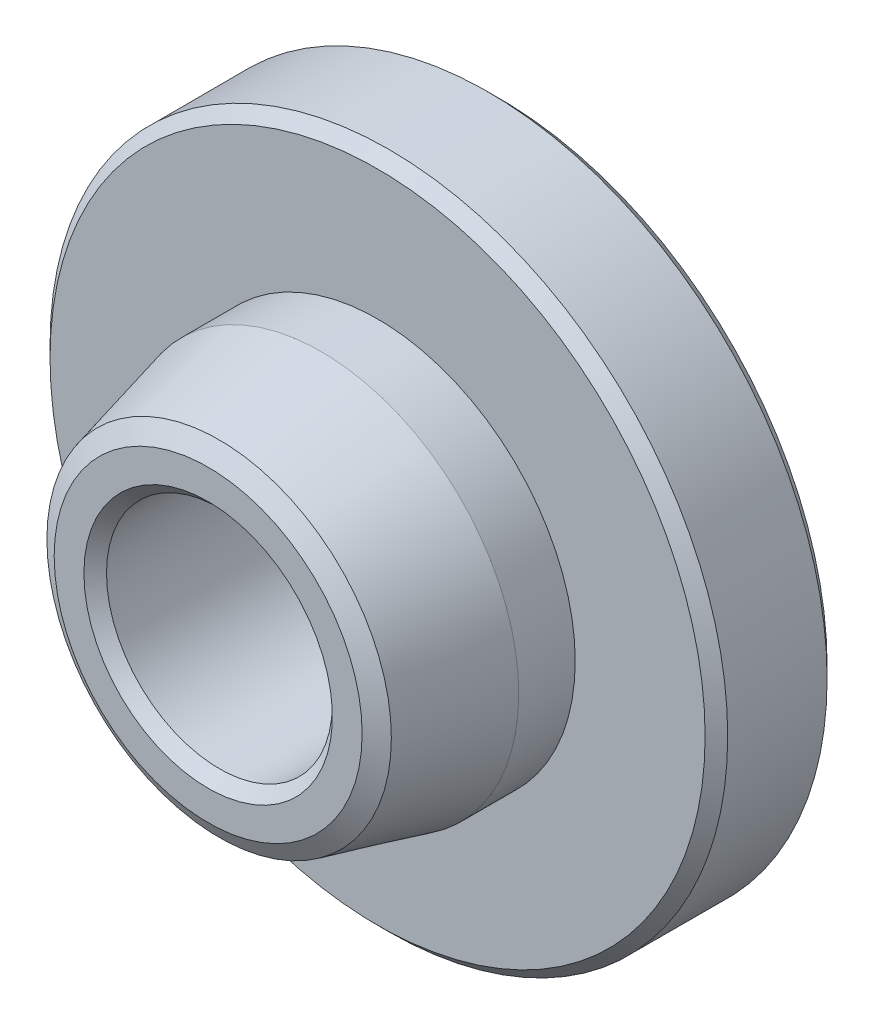
SolidWorks part; units mm, degrees
ref_plane "Ebene vorne" through (0, 0, 0) normal (0, 0, 1) x (1, 0, 0)
ref_plane "Ebene oben" through (0, 0, 0) normal (0, 1, 0) x (1, 0, 0)
ref_plane "Ebene rechts" through (0, 0, 0) normal (1, 0, 0) x (0, 0, -1)
ref_axis "Achse1" through (0, 0, -1.629) along (0, 0, 1)
sketch "Skizze1" plane through (0, 0, 0) normal (1, 0, 0) x (0, 0, -1)
  line L0 (0, 21.2) -> (0, -20.4348) construction
  line L1 (-23.4087, 0) -> (24.2783, 0) construction
  line L2 (0, 2) -> (-4.66, 2)
  line L3 (-4.66, 2) -> (-4.66, 3.0013)
  line L4 (-4.66, 3.0013) -> (-2.66, 3.5)
  line L5 (-2.66, 3.5) -> (-1.66, 3.5)
  line L6 (-1.66, 3.5) -> (-1.66, 6)
  line L7 (-1.66, 6) -> (0, 6)
  line L8 (0, 4.57) -> (0, 2)
  line L9 (0, 4.57) -> (1.3, 4.57)
  line L10 (1.3, 4.57) -> (1.3, 6)
  line L11 (1.3, 6) -> (0, 6)
  point P7 (-4.66, 2.5007)
  dimension "D1" = 4
  dimension "D2" = 7
  dimension "D3" = 3
  dimension "D4" = 1
  dimension "D5" = 4.66
  dimension "D6" = 14
  dimension "D7" = 12
  dimension "D8" = 9.14
  dimension "D9" = 1.3
revolve "Rotation1" add sketch "Skizze1" angle 360 about L1
sketch "Skizze4" plane through (0, 0, 0) normal (0, 0, -1) x (-1, 0, 0)
  line L0 (0, 10.9843) -> (0, -8.8898) construction
  line L1 (-8.6691, 0) -> (11.202, 0) construction
  line L2 (-0.8085, 3.57) -> (-1.2, 4.4096)
  line L3 (0.8085, 3.57) -> (1.2, 4.4096)
  line L4 (-0.8085, 3.57) -> (0.8085, 3.57)
  line L5 (-1.7231, 4.57) -> (1.4652, 4.57) construction
  circle A0 centre (0, 0) radius 4.57 construction
  arc A2 (-1.2, 4.4096) -> (1.2, 4.4096) centre (0, 0) cw
  dimension "D1" = 9.14
  dimension "D2" = 1
  dimension "D3" = 50
  dimension "D4" = 2.4
  dimension "D5" = 1.6169
extrude "Aufsatz-Linear austragen1" add sketch "Skizze4" along normal up to surface (1.3 mm away) up to face at (6, 0, -1.3)
fillet "Verrundung1" radius 0.5 2 edges at (-0.8085, 3.57, -0.65) (0.8085, 3.57, -0.65)
pattern_circular "Kreismuster1" count 10 over 360 about axis through (0, 0, -1.629) along (0, 0, 1) of "Aufsatz-Linear austragen1", "Verrundung1"
sketch "Skizze5" plane through (0, 0, 0) normal (1, 0, 0) x (0, 0, -1)
  line L0 (0.5, 6) -> (0.5, 5)
  line L1 (0.5, 5) -> (1.1536, 4.3464)
  line L2 (1.3, 3.9929) -> (1.3, 2.5972)
  line L3 (1.3, 2.5972) -> (2.5353, 2.5972)
  line L4 (2.5353, 2.5972) -> (2.5353, 6)
  line L5 (2.5353, 6) -> (0.5, 6)
  line L6 (4.9819, 0) -> (-6.4618, 0) construction
  line L7 (0, -7.6291) -> (0, 9.1209) construction
  line L8 (1.3, 6) -> (-1.66, 6) construction
  line L10 (1.3, -6) -> (1.3, 6) construction
  arc A0 (1.1536, 4.3464) -> (1.3, 3.9929) centre (0.8, 3.9929) cw
  dimension "D4" = 0.5
  dimension "D1" = 10
  dimension "D2" = 45
  dimension "D3" = 0.5
revolve "Schnitt-Rotation1" cut sketch "Skizze5" angle 360 about L6
chamfer "Fase1" distance 0.2 angle 45 5 edges at (6, 0, 1.66) (-6, 0, -0.5) (2, 0, 0) (2, 0, 4.66) (3.0013, 0, 4.66) first distance on face at (-6, 0, -0.5) first distance on face at (2, 0, 0) first distance on face at (2, 0, 4.66) first distance on face at (3.0013, 0, 4.66)
